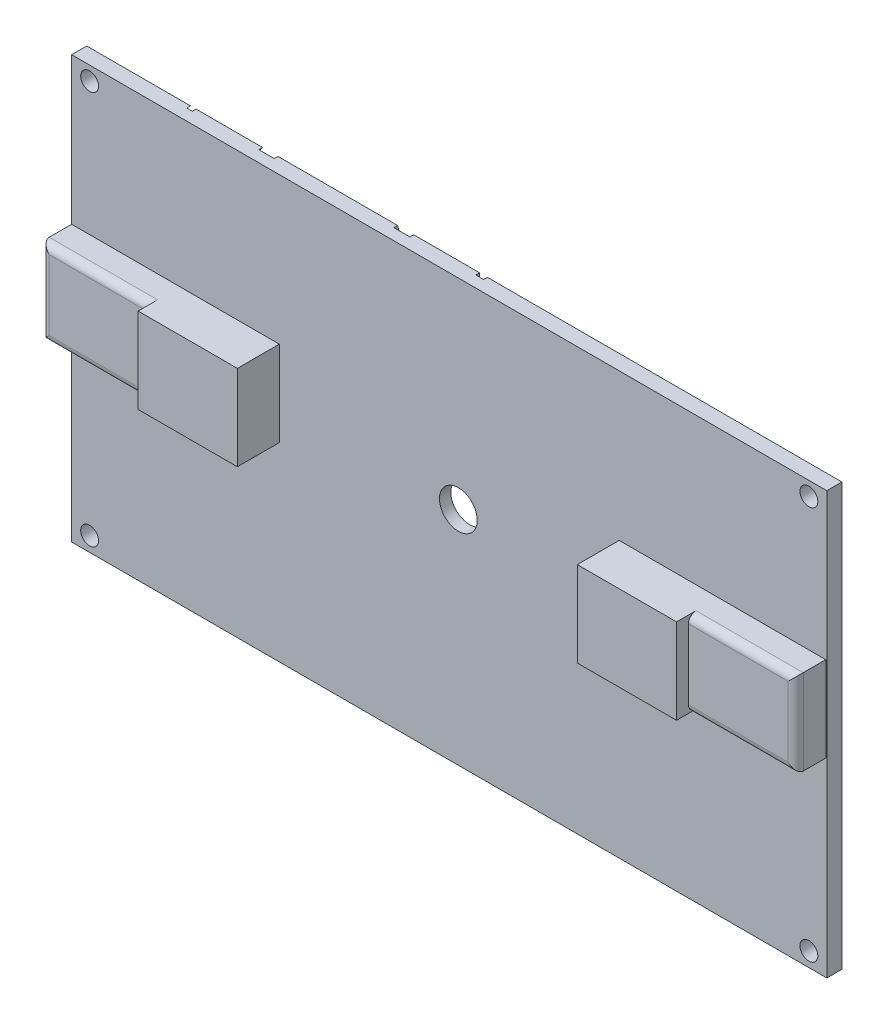
SolidWorks part; units mm, degrees
note: The reader was unsure of these and kept them because the rebuilt part matched: shared geometry of "Sketch2<4>".
ref_plane "Front Plane" through (0, 0, 0) normal (0, 0, 1) x (1, 0, 0)
ref_plane "Top Plane" through (0, 0, 0) normal (0, 1, 0) x (1, 0, 0)
ref_plane "Right Plane" through (0, 0, 0) normal (1, 0, 0) x (0, 0, -1)
sketch "Sketch1" plane through (0, 0, 0) normal (0, 0, 1) x (1, 0, 0)
  line L0 (-63.5, 34.2153) -> (63.5, 34.2153)
  line L1 (-63.5, 34.2153) -> (-63.5, -36.7553)
  line L2 (63.5, 34.2153) -> (63.5, -36.7553)
  line L3 (-63.5, -36.7553) -> (63.5, -36.7553)
  line L5 (63.5, -36.7553) -> (-63.5, -36.7553) construction
  line L18 (-53.34, 34.2153) -> (-63.5, 34.2153) construction
  circle A0 centre (-60.4829, 31.8742) radius 1.5
  circle A1 centre (60.4829, 31.8742) radius 1.5
  circle A2 centre (60.4829, -34.3039) radius 1.5
  circle A3 centre (-60.4829, -34.3039) radius 1.5
extrude "Boss-Extrude1" add sketch "Sketch1" along normal blind 2.54
sketch "Sketch2" plane through (0, 0, 2.54) normal (0, 0, 1) x (1, 0, 0)
  line L4 (-28.5843, 9.5211) -> (-45.2716, 9.5211)
  line L5 (-28.5843, 9.5211) -> (-28.5843, -4.8138)
  line L7 (-45.2716, 9.5211) -> (-45.2716, -4.8138)
  line L15 (-45.2716, 9.5211) -> (-45.2716, -4.8138)
  line L16 (0, 36.7553) -> (0, -36.7553)
  line L17 (-63.5, -36.7553) -> (63.5, -36.7553) construction
  line L22 (-28.5843, -4.8138) -> (-45.2716, -4.8138)
  line L23 (45.2716, 9.5211) -> (45.2716, -4.8138)
  line L24 (28.5843, -4.8138) -> (45.2716, -4.8138)
  line L25 (28.5843, 9.5211) -> (28.5843, -4.8138)
  line L26 (28.5843, 9.5211) -> (45.2716, 9.5211)
  line L27 (-45.2716, 9.5211) -> (-63.5092, 9.5211)
  line L28 (-45.2716, -4.8138) -> (-63.5092, -4.8138)
  line L29 (-63.5092, 9.5211) -> (-63.5092, -4.8138)
  line L30 (45.2716, 9.5211) -> (45.2716, -4.8138)
  line L31 (45.2716, 9.5211) -> (63.3189, 9.5211)
  line L32 (45.2716, -4.8138) -> (63.3189, -4.8138)
  line L33 (63.3189, 9.5211) -> (63.3189, -4.8138)
  point P13 (0, 0)
  point P19 (0, 0)
  line M8 (-63.5, 34.2153) -> (-63.5, -36.7553)
extrude "Boss-Extrude2" add sketch "Sketch2" along normal up to surface (7.05 mm away) contours L22 L5 L4 L7 | L26 L25 L24 L23
sketch "Sketch5" plane through (0, 0, 0) normal (0, 0, -1) x (-1, 0, 0)
  line L0 (-36.885, -13.4809) -> (-37.1458, -14.3716)
  line L1 (-37.1458, -14.3716) -> (-36.8589, -14.6391)
  line L2 (-27.5225, -14.1108) -> (-27.83, -13.4309)
  line L4 (-31.7769, -13.0748) -> (-31.7416, -14.0911)
  line L5 (-32.5586, -12.7895) -> (-32.5586, -11.5305)
  line L6 (-40.1865, -10.7947) -> (-40.5841, -11.2787)
  line L7 (-24.1261, -11.1687) -> (-24.6946, -10.6003)
  line L9 (-28.8243, -9.1813) -> (-28.4608, -9.8868)
  line L10 (-28.4608, -9.8868) -> (-27.9672, -9.3035)
  line L11 (-39.308, -8.9338) -> (-39.0341, -8.7828)
  line L12 (-40.0462, -9.507) -> (-39.308, -8.9338)
  line L14 (-32.7102, -6.0212) -> (-32.7102, -4.7967)
  line L15 (-30.3226, -4.27) -> (-29.7412, -6.9873)
  line L16 (-35.3662, -3.9608) -> (-35.7336, -5.255)
  line L17 (-32.05, -1.5921) -> (-30.4169, -0.7505)
  line L18 (-32.8547, 1.5812) -> (-32.6594, 1.6396)
  line L19 (-31.2175, 1.5222) -> (-30.8977, 2.9206)
  line L21 (-28.2771, 4.5462) -> (-27.9991, 5.1262)
  line L24 (-30.2374, 5.2517) -> (-30.134, 5.4911)
  spline S0 degree 3 poles (-33.1885, -17.143) (-34.1932, -17.0103) (-34.7116, -16.8535) (-35.6221, -16.4098) knots 0 0 0 0 0.058824 0.058824 0.058824 0.058824
  spline S1 degree 3 poles (-35.6221, -16.4098) (-36.8909, -15.7906) (-39.1899, -14.0879) (-40.2119, -13.0118) knots 0.058824 0.058824 0.058824 0.058824 0.117647 0.117647 0.117647 0.117647
  spline S2 degree 3 poles (-40.2119, -13.0118) (-42.0998, -11.0241) (-43.4284, -8.8127) (-44.5933, -6.0588) knots 0.117647 0.117647 0.117647 0.117647 0.176471 0.176471 0.176471 0.176471
  spline S3 degree 3 poles (-44.5933, -6.0588) (-46.4838, -1.5902) (-46.9882, 2.0987) (-46.9916, 7.2423) knots 0.176471 0.176471 0.176471 0.176471 0.235294 0.235294 0.235294 0.235294
  spline S4 degree 3 poles (-46.9916, 7.2423) (-46.9929, 9.1941) (-46.9384, 10.3368) (-46.6702, 11.9282) knots 0.235294 0.235294 0.235294 0.235294 0.294118 0.294118 0.294118 0.294118
  spline S5 degree 3 poles (-46.6702, 11.9282) (-46.2271, 14.5594) (-45.4891, 16.6557) (-44.1889, 18.9752) knots 0.294118 0.294118 0.294118 0.294118 0.352941 0.352941 0.352941 0.352941
  spline S6 degree 3 poles (-44.1889, 18.9752) (-42.1802, 22.5589) (-39.5745, 24.3329) (-35.4062, 25.1243) knots 0.352941 0.352941 0.352941 0.352941 0.411765 0.411765 0.411765 0.411765
  spline S7 degree 3 poles (-35.4062, 25.1243) (-32.345, 25.7055) (-28.2421, 25.2315) (-25.7811, 24.0137) knots 0.411765 0.411765 0.411765 0.411765 0.470588 0.470588 0.470588 0.470588
  spline S8 degree 3 poles (-25.7811, 24.0137) (-23.4916, 22.8808) (-21.2928, 20.156) (-20.2719, 17.5728) knots 0.470588 0.470588 0.470588 0.470588 0.529412 0.529412 0.529412 0.529412
  spline S9 degree 3 poles (-20.2719, 17.5728) (-19.4845, 15.5796) (-18.8834, 13.1051) (-18.6988, 11.0973) knots 0.529412 0.529412 0.529412 0.529412 0.588235 0.588235 0.588235 0.588235
  spline S10 degree 3 poles (-18.6988, 11.0973) (-18.611, 10.1466) (-18.5766, 5.6765) (-18.6463, 4.365) knots 0.588235 0.588235 0.588235 0.588235 0.647059 0.647059 0.647059 0.647059
  spline S11 degree 3 poles (-18.6463, 4.365) (-18.8456, 0.6315) (-19.5099, -2.7362) (-20.7517, -6.3131) knots 0.647059 0.647059 0.647059 0.647059 0.705882 0.705882 0.705882 0.705882
  spline S12 degree 3 poles (-20.7517, -6.3131) (-21.6686, -8.9526) (-22.4464, -10.3502) (-23.9554, -12.0678) knots 0.705882 0.705882 0.705882 0.705882 0.764706 0.764706 0.764706 0.764706
  spline S13 degree 3 poles (-23.9554, -12.0678) (-25.7017, -14.0551) (-26.815, -14.7587) (-28.7545, -16.0654) knots 0.764706 0.764706 0.764706 0.764706 0.823529 0.823529 0.823529 0.823529
  spline S14 degree 3 poles (-28.7545, -16.0654) (-29.6402, -16.6615) (-30.2709, -16.9209) (-31.1354, -17.0447) knots 0.823529 0.823529 0.823529 0.823529 0.882353 0.882353 0.882353 0.882353
  spline S15 degree 3 poles (-31.1354, -17.0447) (-31.64, -17.1176) (-32.9193, -17.1783) (-33.1885, -17.143) knots 0.882353 0.882353 0.882353 0.882353 1 1 1 1
  spline S16 degree 3 poles (-32.4855, -15.8005) (-32.534, -14.6332) (-32.4987, -14.7252) (-32.9825, -14.502) knots 0 0 0 0 0.142857 0.142857 0.142857 0.142857
  spline S17 degree 3 poles (-32.9825, -14.502) (-34.4925, -13.8043) (-35.6396, -13.5475) (-36.885, -13.4809) knots 0.142857 0.142857 0.142857 0.142857 0.285714 0.285714 0.285714 0.285714
  spline S18 degree 3 poles (-36.8589, -14.6391) (-35.827, -15.5987) (-34.0406, -16.3533) (-32.5462, -16.4614) knots 0.571429 0.571429 0.571429 0.571429 0.714286 0.714286 0.714286 0.714286
  spline S19 degree 3 poles (-32.5462, -16.4614) (-32.4649, -16.4673) (-32.4601, -16.4148) (-32.4855, -15.8005) knots 0.714286 0.714286 0.714286 0.714286 1 1 1 1
  spline S20 degree 3 poles (-30.8024, -16.1563) (-30.1643, -15.9317) (-29.4926, -15.5921) (-28.8864, -15.1869) knots 0 0 0 0 0.142857 0.142857 0.142857 0.142857
  spline S21 degree 3 poles (-28.8864, -15.1869) (-28.2116, -14.7359) (-27.5258, -14.1944) (-27.5225, -14.1108) knots 0.142857 0.142857 0.142857 0.142857 0.285714 0.285714 0.285714 0.285714
  spline S22 degree 3 poles (-27.83, -13.4309) (-29.6027, -13.6122) (-30.2155, -13.9611) (-31.8031, -14.7546) knots 0.428571 0.428571 0.428571 0.428571 0.571429 0.571429 0.571429 0.571429
  spline S23 degree 3 poles (-31.8031, -14.7546) (-31.8031, -15.0363) (-31.8511, -16.302) (-31.7761, -16.377) knots 0.571429 0.571429 0.571429 0.571429 0.714286 0.714286 0.714286 0.714286
  spline S24 degree 3 poles (-31.7761, -16.377) (-31.7301, -16.423) (-31.2528, -16.3156) (-30.8024, -16.1563) knots 0.714286 0.714286 0.714286 0.714286 1 1 1 1
  spline S25 degree 3 poles (-29.7616, -13.2038) (-27.6822, -12.7041) (-27.7167, -13.5177) (-28.4018, -11.8782) knots 0 0 0 0 0.142857 0.142857 0.142857 0.142857
  spline S27 degree 3 poles (-31.1978, -11.4148) (-31.8861, -11.7602) (-31.8286, -11.5968) (-31.7769, -13.0748) knots 0.428571 0.428571 0.428571 0.428571 0.571429 0.571429 0.571429 0.571429
  spline S28 degree 3 poles (-31.7416, -14.0911) (-31.1726, -13.8005) (-30.2292, -13.3153) (-29.7616, -13.2038) knots 0.714286 0.714286 0.714286 0.714286 1 1 1 1
  spline S29 degree 3 poles (-32.5586, -11.5305) (-33.91, -10.8515) (-34.3275, -10.9556) (-35.9543, -10.9497) knots 0.142857 0.142857 0.142857 0.142857 0.285714 0.285714 0.285714 0.285714
  spline S30 degree 3 poles (-35.9543, -10.9497) (-36.0729, -11.261) (-36.7649, -12.9501) (-36.7022, -13.0133) knots 0.285714 0.285714 0.285714 0.285714 0.428571 0.428571 0.428571 0.428571
  spline S31 degree 3 poles (-36.7022, -13.0133) (-36.6867, -13.0282) (-36.5069, -13.0412) (-36.3028, -13.0412) knots 0.428571 0.428571 0.428571 0.428571 0.571429 0.571429 0.571429 0.571429
  spline S32 degree 3 poles (-36.3028, -13.0412) (-34.1419, -13.0412) (-33.0415, -13.9931) (-32.5962, -14.0445) knots 0.571429 0.571429 0.571429 0.571429 0.714286 0.714286 0.714286 0.714286
  spline S33 degree 3 poles (-32.5962, -14.0445) (-32.5758, -14.0468) (-32.5586, -13.4826) (-32.5586, -12.7895) knots 0.714286 0.714286 0.714286 0.714286 1 1 1 1
  spline S34 degree 3 poles (-37.6832, -13.7696) (-37.5454, -13.4809) (-37.5716, -13.0643) (-37.7463, -12.759) knots 0 0 0 0 0.142857 0.142857 0.142857 0.142857
  spline S35 degree 3 poles (-37.7463, -12.759) (-38.0466, -12.235) (-39.9648, -10.4193) (-40.1865, -10.7947) knots 0.142857 0.142857 0.142857 0.142857 0.285714 0.285714 0.285714 0.285714
  spline S36 degree 3 poles (-40.5841, -11.2787) (-40.1635, -11.9147) (-39.6844, -12.5177) (-39.1061, -12.9969) knots 0.428571 0.428571 0.428571 0.428571 0.571429 0.571429 0.571429 0.571429
  spline S37 degree 3 poles (-39.1061, -12.9969) (-38.6207, -13.3996) (-37.8677, -13.9485) (-37.7997, -13.9485) knots 0.571429 0.571429 0.571429 0.571429 0.714286 0.714286 0.714286 0.714286
  spline S38 degree 3 poles (-37.7997, -13.9485) (-37.7825, -13.9485) (-37.73, -13.8681) (-37.6832, -13.7696) knots 0.714286 0.714286 0.714286 0.714286 1 1 1 1
  spline S39 degree 3 poles (-26.2446, -13.4366) (-25.5545, -12.9738) (-24.5004, -11.8071) (-24.1261, -11.1687) knots 0 0 0 0 0.166667 0.166667 0.166667 0.166667
  spline S40 degree 3 poles (-24.6946, -10.6003) (-25.3891, -10.9385) (-26.2233, -11.6423) (-26.6867, -12.4121) knots 0.333333 0.333333 0.333333 0.333333 0.5 0.5 0.5 0.5
  spline S41 degree 3 poles (-26.6867, -12.4121) (-27.0847, -13.0732) (-26.6331, -13.6457) (-26.5826, -13.6457) knots 0.5 0.5 0.5 0.5 0.666667 0.666667 0.666667 0.666667
  spline S42 degree 3 poles (-26.5826, -13.6457) (-26.5677, -13.6457) (-26.4161, -13.5515) (-26.2446, -13.4366) knots 0.666667 0.666667 0.666667 0.666667 1 1 1 1
  spline S43 degree 3 poles (-37.1901, -12.2973) (-37.0062, -11.8168) (-36.694, -10.683) (-36.8433, -10.2919) knots 0 0 0 0 0.166667 0.166667 0.166667 0.166667
  spline S44 degree 3 poles (-36.8433, -10.2919) (-36.913, -10.1075) (-37.4698, -9.562) (-37.7619, -9.3913) knots 0.166667 0.166667 0.166667 0.166667 0.333333 0.333333 0.333333 0.333333
  spline S45 degree 3 poles (-37.7619, -9.3913) (-38.43, -9.0016) (-38.869, -9.6263) (-39.532, -10.2518) knots 0.333333 0.333333 0.333333 0.333333 0.5 0.5 0.5 0.5
  spline S46 degree 3 poles (-39.532, -10.2518) (-38.7493, -10.782) (-37.8147, -11.4465) (-37.4568, -12.1217) knots 0.5 0.5 0.5 0.5 0.666667 0.666667 0.666667 0.666667
  spline S47 degree 3 poles (-37.4568, -12.1217) (-37.3159, -12.3876) (-37.2922, -12.5683) (-37.1901, -12.2973) knots 0.666667 0.666667 0.666667 0.666667 1 1 1 1
  spline S49 degree 3 poles (-25.2974, -10.1524) (-25.5981, -9.8388) (-26.2691, -9.2125) (-26.5095, -9.1364) knots 0.166667 0.166667 0.166667 0.166667 0.333333 0.333333 0.333333 0.333333
  spline S50 degree 3 poles (-26.5095, -9.1364) (-26.6786, -9.083) (-27.206, -9.3995) (-27.6037, -9.7917) knots 0.333333 0.333333 0.333333 0.333333 0.5 0.5 0.5 0.5
  spline S52 degree 3 poles (-27.5577, -11.6674) (-27.1975, -12.4128) (-27.3214, -12.4753) (-26.9591, -11.7994) knots 0.666667 0.666667 0.666667 0.666667 1 1 1 1
  spline S53 degree 3 poles (-31.3693, -10.6759) (-30.544, -10.3198) (-29.9421, -10.2965) (-29.0718, -10.2543) knots 0 0 0 0 0.166667 0.166667 0.166667 0.166667
  spline S55 degree 3 poles (-30.1005, -7.9322) (-30.565, -7.5949) (-32.033, -8.1301) (-31.9335, -8.3866) knots 0.333333 0.333333 0.333333 0.333333 0.5 0.5 0.5 0.5
  spline S57 degree 3 poles (-32.7028, -9.5382) (-32.7544, -7.9651) (-32.7841, -7.8112) (-33.8266, -7.7609) knots 0 0 0 0 0.142857 0.142857 0.142857 0.142857
  spline S59 degree 3 poles (-35.3506, -9.0822) (-35.8526, -10.4299) (-35.9628, -10.2508) (-34.9651, -10.2788) knots 0.285714 0.285714 0.285714 0.285714 0.428571 0.428571 0.428571 0.428571
  spline S60 degree 3 poles (-34.9651, -10.2788) (-34.1139, -10.3027) (-34.2699, -10.2745) (-33.4657, -10.556) knots 0.428571 0.428571 0.428571 0.428571 0.571429 0.571429 0.571429 0.571429
  spline S61 degree 3 poles (-33.4657, -10.556) (-33.0638, -10.6971) (-32.7192, -10.7973) (-32.6997, -10.7792) knots 0.571429 0.571429 0.571429 0.571429 0.714286 0.714286 0.714286 0.714286
  spline S63 degree 3 poles (-41.0263, -10.7233) (-40.9755, -10.6963) (-40.8279, -10.5331) (-40.6982, -10.3609) knots 0 0 0 0 0.125 0.125 0.125 0.125
  spline S64 degree 3 poles (-40.6982, -10.3609) (-40.4176, -9.9876) (-40.4193, -9.936) (-40.7317, -9.4152) knots 0.125 0.125 0.125 0.125 0.25 0.25 0.25 0.25
  spline S65 degree 3 poles (-40.7317, -9.4152) (-41.0574, -8.8714) (-41.575, -8.2505) (-41.8383, -8.088) knots 0.25 0.25 0.25 0.25 0.375 0.375 0.375 0.375
  spline S66 degree 3 poles (-41.8383, -8.088) (-42.1056, -7.9232) (-42.9079, -7.6313) (-42.9282, -7.6912) knots 0.375 0.375 0.375 0.375 0.5 0.5 0.5 0.5
  spline S67 degree 3 poles (-42.9282, -7.6912) (-42.9522, -7.7609) (-42.5912, -8.6121) (-42.3262, -9.1101) knots 0.5 0.5 0.5 0.5 0.625 0.625 0.625 0.625
  spline S68 degree 3 poles (-42.3262, -9.1101) (-42.0065, -9.7138) (-41.6932, -10.1886) (-41.3969, -10.5167) knots 0.625 0.625 0.625 0.625 0.75 0.75 0.75 0.75
  spline S69 degree 3 poles (-41.3969, -10.5167) (-41.1421, -10.8004) (-41.1559, -10.793) (-41.0263, -10.7233) knots 0.75 0.75 0.75 0.75 1 1 1 1
  spline S70 degree 3 poles (-23.4839, -10.383) (-22.9736, -9.803) (-21.8591, -7.6985) (-21.9918, -7.5664) knots 0 0 0 0 0.2 0.2 0.2 0.2
  spline S71 degree 3 poles (-21.9918, -7.5664) (-22.0287, -7.5295) (-22.7743, -7.7445) (-22.9843, -7.8518) knots 0.2 0.2 0.2 0.2 0.4 0.4 0.4 0.4
  spline S74 degree 3 poles (-36.1462, -9.5013) (-36.0302, -9.223) (-35.4667, -7.9213) (-35.5883, -7.7033) knots 0 0 0 0 0.2 0.2 0.2 0.2
  spline S75 degree 3 poles (-35.5883, -7.7033) (-35.7448, -7.4227) (-36.3024, -7.2794) (-36.6661, -7.2399) knots 0.2 0.2 0.2 0.2 0.4 0.4 0.4 0.4
  spline S76 degree 3 poles (-36.6661, -7.2399) (-37.8207, -8.7342) (-38.6837, -8.311) (-37.6707, -8.8263) knots 0.4 0.4 0.4 0.4 0.6 0.6 0.6 0.6
  spline S77 degree 3 poles (-37.6707, -8.8263) (-36.2885, -9.5298) (-36.4852, -10.3247) (-36.1462, -9.5013) knots 0.6 0.6 0.6 0.6 1 1 1 1
  spline S79 degree 3 poles (-26.9269, -8.2824) (-27.648, -7.9423) (-28.1494, -6.859) (-28.9922, -7.3934) knots 0.166667 0.166667 0.166667 0.166667 0.333333 0.333333 0.333333 0.333333
  spline S81 degree 3 poles (-39.0341, -8.7828) (-39.544, -8.7577) (-40.2985, -8.6688) (-40.5743, -8.5499) knots 0.2 0.2 0.2 0.2 0.4 0.4 0.4 0.4
  spline S82 degree 3 poles (-40.5743, -8.5499) (-41.2357, -8.2647) (-40.5004, -8.786) (-40.0462, -9.507) knots 0.4 0.4 0.4 0.4 0.6 0.6 0.6 0.6
  spline S84 degree 3 poles (-25.8534, -8.6369) (-25.9151, -8.6984) (-25.2754, -8.8894) (-25.0595, -9.1469) knots 0.4 0.4 0.4 0.4 0.6 0.6 0.6 0.6
  spline S85 degree 3 poles (-25.0595, -9.1469) (-24.8511, -9.3938) (-24.8306, -9.3865) (-24.5665, -8.9722) knots 0.6 0.6 0.6 0.6 1 1 1 1
  spline S86 degree 3 poles (-31.425, -7.2227) (-31.1311, -7.1656) (-30.2915, -7.1967) (-30.2915, -7.1941) knots 0 0 0 0 0.166667 0.166667 0.166667 0.166667
  spline S87 degree 3 poles (-30.2915, -7.1941) (-30.2915, -7.1169) (-30.8444, -4.6678) (-30.8715, -4.6235) knots 0.166667 0.166667 0.166667 0.166667 0.333333 0.333333 0.333333 0.333333
  spline S88 degree 3 poles (-30.8715, -4.6235) (-30.9698, -4.4647) (-31.7349, -4.6441) (-32.0049, -4.736) knots 0.333333 0.333333 0.333333 0.333333 0.5 0.5 0.5 0.5
  spline S89 degree 3 poles (-32.0049, -4.736) (-32.0049, -5.2429) (-32.0736, -7.3732) (-31.9163, -7.3268) knots 0.5 0.5 0.5 0.5 0.666667 0.666667 0.666667 0.666667
  spline S90 degree 3 poles (-31.9163, -7.3268) (-31.868, -7.313) (-31.6465, -7.2661) (-31.425, -7.2227) knots 0.666667 0.666667 0.666667 0.666667 1 1 1 1
  spline S91 degree 3 poles (-32.7102, -4.7967) (-34.1565, -4.3301) (-33.9232, -4.5892) (-34.2932, -5.8703) knots 0.142857 0.142857 0.142857 0.142857 0.285714 0.285714 0.285714 0.285714
  spline S93 degree 3 poles (-34.6033, -7.0144) (-34.636, -7.1941) (-34.6312, -7.208) (-34.5443, -7.1736) knots 0.428571 0.428571 0.428571 0.428571 0.571429 0.571429 0.571429 0.571429
  spline S95 degree 3 poles (-32.7725, -7.2416) (-32.7243, -7.245) (-32.7102, -6.9693) (-32.7102, -6.0212) knots 0.714286 0.714286 0.714286 0.714286 1 1 1 1
  spline S96 degree 3 poles (-29.0941, -6.5273) (-28.6897, -6.4338) (-28.8108, -6.4448) (-29.1014, -5.6471) knots 0 0 0 0 0.2 0.2 0.2 0.2
  spline S97 degree 3 poles (-29.1014, -5.6471) (-29.6437, -4.1585) (-29.3659, -3.5407) (-30.3226, -4.27) knots 0.2 0.2 0.2 0.2 0.4 0.4 0.4 0.4
  spline S98 degree 3 poles (-29.7412, -6.9873) (-29.7409, -6.9888) (-29.4018, -6.5981) (-29.0941, -6.5273) knots 0.6 0.6 0.6 0.6 1 1 1 1
  spline S99 degree 3 poles (-35.0823, -6.592) (-34.8855, -5.944) (-34.614, -4.7538) (-34.6067, -4.5071) knots 0 0 0 0 0.166667 0.166667 0.166667 0.166667
  spline S100 degree 3 poles (-34.6067, -4.5071) (-34.5963, -4.1455) (-34.7391, -4.1723) (-35.3662, -3.9608) knots 0.166667 0.166667 0.166667 0.166667 0.333333 0.333333 0.333333 0.333333
  spline S101 degree 3 poles (-35.7336, -5.255) (-36.4029, -7.0592) (-36.1231, -6.1325) (-35.4398, -6.7683) knots 0.5 0.5 0.5 0.5 0.666667 0.666667 0.666667 0.666667
  spline S102 degree 3 poles (-35.4398, -6.7683) (-35.1622, -7.0266) (-35.2038, -6.9907) (-35.0823, -6.592) knots 0.666667 0.666667 0.666667 0.666667 1 1 1 1
  spline S103 degree 3 poles (-39.1267, -5.5545) (-36.8622, -5.0869) (-35.39, -1.9574) (-36.1158, 0.0639) knots 0 0 0 0 0.125 0.125 0.125 0.125
  spline S104 degree 3 poles (-36.1158, 0.0639) (-36.4504, 0.9964) (-36.9884, 1.8823) (-37.9366, 3.0617) knots 0.125 0.125 0.125 0.125 0.25 0.25 0.25 0.25
  spline S105 degree 3 poles (-37.9366, 3.0617) (-39.6049, 5.1378) (-41.0341, 6.4115) (-43.4622, 7.9026) knots 0.25 0.25 0.25 0.25 0.375 0.375 0.375 0.375
  spline S106 degree 3 poles (-43.4622, 7.9026) (-45.2972, 9.0294) (-45.1867, 9.9658) (-45.4357, 10.2329) knots 0.375 0.375 0.375 0.375 0.5 0.5 0.5 0.5
  spline S107 degree 3 poles (-45.4357, 10.2329) (-45.4823, 10.282) (-45.6325, 9.8595) (-45.8122, 9.1706) knots 0.5 0.5 0.5 0.5 0.625 0.625 0.625 0.625
  spline S108 degree 3 poles (-45.8122, 9.1706) (-46.3428, 7.1307) (-46.4658, 5.2672) (-46.1904, 3.412) knots 0.625 0.625 0.625 0.625 0.75 0.75 0.75 0.75
  spline S109 degree 3 poles (-46.1904, 3.412) (-45.7116, 0.1923) (-43.6372, -6.4835) (-39.1267, -5.5545) knots 0.75 0.75 0.75 0.75 1 1 1 1
  spline S110 degree 3 poles (-24.7002, -5.4052) (-20.3571, -4.3647) (-18.9082, 3.5793) (-19.5616, 7.444) knots 0 0 0 0 0.125 0.125 0.125 0.125
  spline S111 degree 3 poles (-19.5616, 7.444) (-19.7709, 8.6821) (-20.1311, 9.9316) (-20.4771, 10.6142) knots 0.125 0.125 0.125 0.125 0.25 0.25 0.25 0.25
  spline S112 degree 3 poles (-20.4771, 10.6142) (-20.8251, 9.2389) (-21.1954, 8.9597) (-22.7227, 7.9017) knots 0.25 0.25 0.25 0.25 0.375 0.375 0.375 0.375
  spline S113 degree 3 poles (-22.7227, 7.9017) (-25.2154, 6.1751) (-28.0616, 2.6127) (-28.8832, 0.1608) knots 0.375 0.375 0.375 0.375 0.5 0.5 0.5 0.5
  spline S114 degree 3 poles (-28.8832, 0.1608) (-29.4311, -1.4747) (-29.2442, -2.7772) (-28.2763, -4.0618) knots 0.5 0.5 0.5 0.5 0.625 0.625 0.625 0.625
  spline S115 degree 3 poles (-28.2763, -4.0618) (-27.6996, -4.8269) (-27.0491, -5.3109) (-26.3981, -5.4594) knots 0.625 0.625 0.625 0.625 0.75 0.75 0.75 0.75
  spline S116 degree 3 poles (-26.3981, -5.4594) (-26.0174, -5.5463) (-25.18, -5.5192) (-24.7002, -5.4052) knots 0.75 0.75 0.75 0.75 1 1 1 1
  spline S117 degree 3 poles (-32.7062, -2.4148) (-32.7804, -1.9319) (-32.7727, -2.0679) (-33.3008, -1.9974) knots 0 0 0 0 0.2 0.2 0.2 0.2
  spline S118 degree 3 poles (-33.3008, -1.9974) (-33.4549, -2.4841) (-33.8184, -3.6255) (-33.8184, -3.873) knots 0.2 0.2 0.2 0.2 0.4 0.4 0.4 0.4
  spline S119 degree 3 poles (-33.8184, -3.873) (-33.3546, -3.9894) (-33.1169, -4.0249) (-32.6848, -4.1978) knots 0.4 0.4 0.4 0.4 0.6 0.6 0.6 0.6
  spline S120 degree 3 poles (-32.6848, -4.1978) (-32.6753, -3.6991) (-32.6463, -2.7926) (-32.7062, -2.4148) knots 0.6 0.6 0.6 0.6 1 1 1 1
  spline S121 degree 3 poles (-31.7105, -4.0708) (-30.8112, -3.7845) (-30.9289, -4.3462) (-31.2184, -2.8954) knots 0 0 0 0 0.2 0.2 0.2 0.2
  spline S122 degree 3 poles (-31.2184, -2.8954) (-31.3793, -2.0887) (-31.335, -1.8889) (-31.7006, -1.998) knots 0.2 0.2 0.2 0.2 0.4 0.4 0.4 0.4
  spline S123 degree 3 poles (-31.7006, -1.998) (-32.0255, -2.0956) (-32.0548, -2.2014) (-32.0548, -3.262) knots 0.4 0.4 0.4 0.4 0.6 0.6 0.6 0.6
  spline S124 degree 3 poles (-32.0548, -3.262) (-32.0548, -4.3234) (-32.1782, -4.2167) (-31.7105, -4.0708) knots 0.6 0.6 0.6 0.6 1 1 1 1
  spline S126 degree 3 poles (-34.2113, -1.4657) (-34.509, -1.3697) (-34.528, -1.3943) (-34.8624, -2.322) knots 0.2 0.2 0.2 0.2 0.4 0.4 0.4 0.4
  spline S127 degree 3 poles (-34.8624, -2.322) (-35.3837, -3.7655) (-35.2588, -3.0877) (-34.5853, -3.6196) knots 0.4 0.4 0.4 0.4 0.6 0.6 0.6 0.6
  spline S129 degree 3 poles (-29.9766, -3.4392) (-29.7239, -3.3767) (-29.8741, -3.2177) (-30.006, -2.8511) knots 0 0 0 0 0.166667 0.166667 0.166667 0.166667
  spline S130 degree 3 poles (-30.006, -2.8511) (-30.3683, -1.8434) (-30.2737, -1.4102) (-30.5326, -1.4739) knots 0.166667 0.166667 0.166667 0.166667 0.333333 0.333333 0.333333 0.333333
  spline S131 degree 3 poles (-30.5326, -1.4739) (-30.8041, -1.5413) (-30.8961, -1.6389) (-30.8961, -1.8602) knots 0.333333 0.333333 0.333333 0.333333 0.5 0.5 0.5 0.5
  spline S132 degree 3 poles (-30.8961, -1.8602) (-30.8961, -2.0834) (-30.5145, -3.5515) (-30.4293, -3.6574) knots 0.5 0.5 0.5 0.5 0.666667 0.666667 0.666667 0.666667
  spline S133 degree 3 poles (-30.4293, -3.6574) (-30.3617, -3.7404) (-30.0767, -3.4641) (-29.9766, -3.4392) knots 0.666667 0.666667 0.666667 0.666667 1 1 1 1
  spline S134 degree 3 poles (-30.4169, -0.7505) (-30.1176, 0.7533) (-30.1764, -0.0351) (-30.8624, 0.5683) knots 0.111111 0.111111 0.111111 0.111111 0.222222 0.222222 0.222222 0.222222
  spline S135 degree 3 poles (-30.8624, 0.5683) (-31.0674, 0.7489) (-31.1552, 0.7848) (-31.6604, 0.8988) knots 0.222222 0.222222 0.222222 0.222222 0.333333 0.333333 0.333333 0.333333
  spline S139 degree 3 poles (-33.8184, -1.0246) (-33.4389, -1.42) (-33.0604, -1.3263) (-32.6487, -1.6043) knots 0.666667 0.666667 0.666667 0.666667 0.777778 0.777778 0.777778 0.777778
  spline S140 degree 3 poles (-32.6487, -1.6043) (-32.3615, -1.7982) (-32.3358, -1.7992) (-32.05, -1.5921) knots 0.777778 0.777778 0.777778 0.777778 1 1 1 1
  spline S141 degree 3 poles (-34.2006, 0.9972) (-34.0586, 1.1384) (-34.1136, 1.4426) (-34.5048, 2.6911) knots 0 0 0 0 0.166667 0.166667 0.166667 0.166667
  spline S142 degree 3 poles (-34.5048, 2.6911) (-35.1391, 4.7129) (-34.6933, 3.7976) (-35.6958, 3.4184) knots 0.166667 0.166667 0.166667 0.166667 0.333333 0.333333 0.333333 0.333333
  spline S143 degree 3 poles (-35.6958, 3.4184) (-36.0946, 3.2676) (-35.9123, 3.1341) (-35.6597, 2.6886) knots 0.333333 0.333333 0.333333 0.333333 0.5 0.5 0.5 0.5
  spline S144 degree 3 poles (-35.6597, 2.6886) (-34.7367, 1.0615) (-35.137, 0.9177) (-34.5795, 0.9177) knots 0.5 0.5 0.5 0.5 0.666667 0.666667 0.666667 0.666667
  spline S145 degree 3 poles (-34.5795, 0.9177) (-34.3736, 0.9177) (-34.2548, 0.9431) (-34.2006, 0.9972) knots 0.666667 0.666667 0.666667 0.666667 1 1 1 1
  spline S146 degree 3 poles (-29.8798, 1.1827) (-29.719, 1.4739) (-28.6281, 3.7491) (-28.6281, 3.7918) knots 0 0 0 0 0.166667 0.166667 0.166667 0.166667
  spline S147 degree 3 poles (-28.6281, 3.7918) (-28.6281, 3.8532) (-29.0899, 3.818) (-29.5098, 4.2018) knots 0.166667 0.166667 0.166667 0.166667 0.333333 0.333333 0.333333 0.333333
  spline S148 degree 3 poles (-29.5098, 4.2018) (-29.9217, 4.5785) (-29.7856, 4.6422) (-30.1981, 2.9821) knots 0.333333 0.333333 0.333333 0.333333 0.5 0.5 0.5 0.5
  spline S149 degree 3 poles (-30.1981, 2.9821) (-30.5842, 1.4288) (-30.5966, 1.2803) (-30.3522, 1.1474) knots 0.5 0.5 0.5 0.5 0.666667 0.666667 0.666667 0.666667
  spline S150 degree 3 poles (-30.3522, 1.1474) (-30.1456, 1.035) (-29.9529, 1.0497) (-29.8798, 1.1827) knots 0.666667 0.666667 0.666667 0.666667 1 1 1 1
  spline S152 degree 3 poles (-32.7669, 4.899) (-32.8268, 4.899) (-33.4484, 4.2945) (-33.9282, 4.2945) knots 0.285714 0.285714 0.285714 0.285714 0.428571 0.428571 0.428571 0.428571
  spline S153 degree 3 poles (-33.9282, 4.2945) (-33.9791, 4.2945) (-34.0202, 4.2716) (-34.0202, 4.2428) knots 0.428571 0.428571 0.428571 0.428571 0.571429 0.571429 0.571429 0.571429
  spline S157 degree 3 poles (-31.5079, 4.7776) (-31.6547, 4.8718) (-31.7924, 4.9489) (-31.8139, 4.9489) knots 0.166667 0.166667 0.166667 0.166667 0.333333 0.333333 0.333333 0.333333
  spline S158 degree 3 poles (-31.8139, 4.9489) (-31.8474, 4.9489) (-31.8835, 3.248) (-31.8762, 2.044) knots 0.333333 0.333333 0.333333 0.333333 0.5 0.5 0.5 0.5
  spline S159 degree 3 poles (-31.8762, 2.044) (-31.8725, 1.4229) (-31.6516, 1.5222) (-31.2175, 1.5222) knots 0.5 0.5 0.5 0.5 0.666667 0.666667 0.666667 0.666667
  spline S160 degree 3 poles (-35.6433, 4.1271) (-34.907, 4.587) (-35.2459, 4.9573) (-35.827, 6.1063) knots 0 0 0 0 0.2 0.2 0.2 0.2
  spline S162 degree 3 poles (-36.4315, 3.9279) (-36.1587, 3.9566) (-35.879, 3.9811) (-35.6433, 4.1271) knots 0.6 0.6 0.6 0.6 1 1 1 1
  spline S163 degree 3 poles (-27.9991, 5.1262) (-27.609, 5.9416) (-27.845, 5.5444) (-27.3675, 6.3434) knots 0 0 0 0 0.166667 0.166667 0.166667 0.166667
  spline S164 degree 3 poles (-27.3675, 6.3434) (-27.0093, 6.9425) (-26.8973, 6.9597) (-27.2715, 7.1604) knots 0.166667 0.166667 0.166667 0.166667 0.333333 0.333333 0.333333 0.333333
  spline S167 degree 3 poles (-33.7643, 5.0729) (-33.5084, 5.139) (-33.0866, 5.4119) (-32.8194, 5.5788) knots 0 0 0 0 0.142857 0.142857 0.142857 0.142857
  spline S170 degree 3 poles (-34.5443, 5.2492) (-34.3125, 4.853) (-34.2195, 4.9583) (-33.7643, 5.0729) knots 0.714286 0.714286 0.714286 0.714286 1 1 1 1
extrude "Cut-Extrude1" cut sketch "Sketch5" against normal blind 0.635
sketch "Sketch7" plane through (0, 0, 0) normal (0, 0, -1) x (-1, 0, 0)
  line L0 (-48.7045, 33.1044) -> (-48.7045, -33.6615)
  line L1 (-33.7488, -48.6172) -> (33.3567, -48.6172)
  line L2 (48.3125, -33.6615) -> (48.3125, 33.1044)
  line L3 (33.3567, 48.0601) -> (-33.7488, 48.0601)
  line L4 (19.1455, 5.8466) -> (27.9776, 5.535)
  line L5 (34.9499, -20.3776) -> (24.2152, -35.5754)
  line L6 (22.349, -34.3309) -> (33.6683, -12.3768)
  line L7 (31.1493, -7.2142) -> (24.6188, -6.2198)
  line L8 (-32.027, -16.991) -> (-24.4193, -33.2625)
  line L9 (-28.6808, 5.7223) -> (-20.0986, 5.9086)
  line L10 (13.7349, 22.8248) -> (10.1278, 33.7714)
  spline S0 degree 3 poles (-33.7488, 48.0601) (-42.0345, 48.0601) (-48.7045, 41.3902) (-48.7045, 33.1044) knots 0 0 0 0 1 1 1 1
  spline S1 degree 3 poles (-48.7045, -33.6615) (-48.7045, -41.9471) (-42.0345, -48.6172) (-33.7488, -48.6172) knots 0 0 0 0 1 1 1 1
  spline S2 degree 3 poles (33.3567, -48.6172) (41.6422, -48.6172) (48.3125, -41.9471) (48.3125, -33.6615) knots 0 0 0 0 1 1 1 1
  spline S3 degree 3 poles (48.3125, 33.1044) (48.3125, 41.3902) (41.6422, 48.0601) (33.3567, 48.0601) knots 0 0 0 0 1 1 1 1
  spline S4 degree 3 poles (11.9314, 35.0149) (18.6333, 26.152) (23.5941, 13.0893) (19.1455, 5.8466) knots 0.5 0.5 0.5 0.5 1 1 1 1
  spline S5 degree 3 poles (10.0057, 36.7203) (10.4586, 36.7312) (11.182, 36.1603) (11.9314, 35.0149) knots 0 0 0 0 0.5 0.5 0.5 0.5
  spline S6 degree 3 poles (39.0511, -5.437) (39.5769, -8.5674) (39.0591, -13.1128) (34.9499, -20.3776) knots 0.833333 0.833333 0.833333 0.833333 1 1 1 1
  spline S7 degree 3 poles (21.8827, 0.4353) (29.5291, -1.2382) (38.4594, -1.9155) (39.0511, -5.437) knots 0.666667 0.666667 0.666667 0.666667 0.833333 0.833333 0.833333 0.833333
  spline S8 degree 3 poles (33.2798, 2.9297) (31.7276, 0.5257) (28.4044, 0.6921) (21.8827, 0.4353) knots 0.5 0.5 0.5 0.5 0.666667 0.666667 0.666667 0.666667
  spline S9 degree 3 poles (26.4224, 32.5897) (32.2138, 25.9838) (36.9653, 8.6368) (33.2798, 2.9297) knots 0.333333 0.333333 0.333333 0.333333 0.5 0.5 0.5 0.5
  spline S10 degree 3 poles (24.3088, 30.9106) (23.1793, 33.6794) (23.1063, 36.3055) (26.4224, 32.5897) knots 0.166667 0.166667 0.166667 0.166667 0.333333 0.333333 0.333333 0.333333
  spline S11 degree 3 poles (27.9776, 5.535) (32.7356, 10.4633) (26.9546, 23.8005) (24.3088, 30.9106) knots 0 0 0 0 0.166667 0.166667 0.166667 0.166667
  spline S12 degree 3 poles (24.2152, -35.5754) (22.0587, -37.8135) (21.4791, -36.3746) (22.349, -34.3309) knots 0 0 0 0 1 1 1 1
  spline S13 degree 3 poles (33.6683, -12.3768) (35.3465, -9.313) (34.747, -7.4643) (31.1493, -7.2142) knots 0 0 0 0 1 1 1 1
  spline S14 degree 3 poles (-35.7616, -8.388) (-36.0162, -9.0988) (-34.7538, -12.2673) (-32.027, -16.991) knots 0.916667 0.916667 0.916667 0.916667 1 1 1 1
  spline S15 degree 3 poles (-25.6511, -5.9088) (-31.0497, -5.9319) (-35.194, -6.8067) (-35.7616, -8.388) knots 0.833333 0.833333 0.833333 0.833333 0.916667 0.916667 0.916667 0.916667
  spline S16 degree 3 poles (-15.8436, -32.4275) (-19.7209, -26.2181) (-27.2095, -17.3361) (-25.6511, -5.9088) knots 0.75 0.75 0.75 0.75 0.833333 0.833333 0.833333 0.833333
  spline S17 degree 3 poles (-14.0408, -31.2846) (-12.4871, -34.8012) (-14.5729, -34.6696) (-15.8436, -32.4275) knots 0.666667 0.666667 0.666667 0.666667 0.75 0.75 0.75 0.75
  spline S18 degree 3 poles (-19.8186, -13.0612) (-19.0817, -20.2054) (-16.3431, -25.5487) (-14.0408, -31.2846) knots 0.583333 0.583333 0.583333 0.583333 0.666667 0.666667 0.666667 0.666667
  spline S19 degree 3 poles (-13.9409, -4.1672) (-19.3397, -3.3567) (-21.2191, -6.4084) (-19.8186, -13.0612) knots 0.5 0.5 0.5 0.5 0.583333 0.583333 0.583333 0.583333
  spline S20 degree 3 poles (-1.3715, -30.2282) (-8.657, -29.6054) (-15.5753, -17.9031) (-13.9409, -4.1672) knots 0.416667 0.416667 0.416667 0.416667 0.5 0.5 0.5 0.5
  spline S21 degree 3 poles (12.7856, -4.3693) (15.0651, -21.3611) (4.6078, -30.7387) (-1.3715, -30.2282) knots 0.333333 0.333333 0.333333 0.333333 0.416667 0.416667 0.416667 0.416667
  spline S22 degree 3 poles (18.8546, -7.2721) (18.4144, -4.0523) (14.8026, -4.651) (12.7856, -4.3693) knots 0.25 0.25 0.25 0.25 0.333333 0.333333 0.333333 0.333333
  spline S23 degree 3 poles (12.3977, -31.0347) (16.4864, -23.3035) (19.772, -15.469) (18.8546, -7.2721) knots 0.166667 0.166667 0.166667 0.166667 0.25 0.25 0.25 0.25
  spline S24 degree 3 poles (14.2949, -32.5274) (11.6918, -36.3176) (10.971, -33.7185) (12.3977, -31.0347) knots 0.083333 0.083333 0.083333 0.083333 0.166667 0.166667 0.166667 0.166667
  spline S25 degree 3 poles (24.6188, -6.2198) (25.6872, -15.4848) (20.9778, -24.0846) (14.2949, -32.5274) knots 0 0 0 0 0.083333 0.083333 0.083333 0.083333
  spline S26 degree 3 poles (-30.298, 10.7591) (-30.2629, 7.1465) (-29.3795, 6.7889) (-28.6808, 5.7223) knots 0.888889 0.888889 0.888889 0.888889 1 1 1 1
  spline S27 degree 3 poles (-24.203, 32.7134) (-26.6186, 25.3707) (-30.0965, 18.9537) (-30.298, 10.7591) knots 0.777778 0.777778 0.777778 0.777778 0.888889 0.888889 0.888889 0.888889
  spline S28 degree 3 poles (-25.8202, 33.6777) (-24.528, 35.2259) (-23.3963, 34.8532) (-24.203, 32.7134) knots 0.666667 0.666667 0.666667 0.666667 0.777778 0.777778 0.777778 0.777778
  spline S29 degree 3 poles (-34.534, 15.7718) (-33.2564, 21.3338) (-31.7025, 26.9649) (-25.8202, 33.6777) knots 0.555556 0.555556 0.555556 0.555556 0.666667 0.666667 0.666667 0.666667
  spline S30 degree 3 poles (-34.1677, 3.3302) (-36.1393, 5.7475) (-35.1478, 8.9899) (-34.534, 15.7718) knots 0.444444 0.444444 0.444444 0.444444 0.555556 0.555556 0.555556 0.555556
  spline S31 degree 3 poles (-22.7483, 0.908) (-27.7767, 0.8239) (-32.1468, 0.8524) (-34.1677, 3.3302) knots 0.333333 0.333333 0.333333 0.333333 0.444444 0.444444 0.444444 0.444444
  spline S32 degree 3 poles (-40.1635, -4.2815) (-38.9739, -1.6157) (-29.0298, -0.725) (-22.7483, 0.908) knots 0.222222 0.222222 0.222222 0.222222 0.333333 0.333333 0.333333 0.333333
  spline S33 degree 3 poles (-26.1348, -34.5823) (-31.8952, -26.6685) (-41.5697, -14.5007) (-40.1635, -4.2815) knots 0.111111 0.111111 0.111111 0.111111 0.222222 0.222222 0.222222 0.222222
  spline S34 degree 3 poles (-24.4193, -33.2625) (-22.2963, -37.758) (-25.3633, -35.8934) (-26.1348, -34.5823) knots 0 0 0 0 0.111111 0.111111 0.111111 0.111111
  spline S35 degree 3 poles (6.2098, 6.9659) (20.11, 6.0386) (17.5823, 14.0721) (13.7349, 22.8248) knots 0.857143 0.857143 0.857143 0.857143 1 1 1 1
  spline S36 degree 3 poles (-0.4905, 22.4345) (4.2762, 22.2682) (13.1377, 16.6742) (6.2098, 6.9659) knots 0.714286 0.714286 0.714286 0.714286 0.857143 0.857143 0.857143 0.857143
  spline S37 degree 3 poles (-7.0993, 7.1522) (-13.3651, 15.9882) (-5.1474, 22.5972) (-0.4905, 22.4345) knots 0.571429 0.571429 0.571429 0.571429 0.714286 0.714286 0.714286 0.714286
  spline S38 degree 3 poles (-17.3193, 11.2638) (-16.7452, 8.4909) (-14.0082, 6.7889) (-7.0993, 7.1522) knots 0.428571 0.428571 0.428571 0.428571 0.571429 0.571429 0.571429 0.571429
  spline S39 degree 3 poles (-10.8936, 32.0917) (-12.0413, 27.5732) (-18.4235, 16.599) (-17.3193, 11.2638) knots 0.285714 0.285714 0.285714 0.285714 0.428571 0.428571 0.428571 0.428571
  spline S40 degree 3 poles (-13.3189, 33.5224) (-12.2744, 35.5138) (-7.8378, 40.0996) (-10.8936, 32.0917) knots 0.142857 0.142857 0.142857 0.142857 0.285714 0.285714 0.285714 0.285714
  spline S41 degree 3 poles (-20.0986, 5.9086) (-24.2068, 13.5525) (-18.7866, 25.7992) (-13.3189, 33.5224) knots 0 0 0 0 0.142857 0.142857 0.142857 0.142857
  spline S42 degree 3 poles (10.1278, 33.7714) (9.2903, 35.7289) (9.4244, 36.7051) (10.0057, 36.7203) knots 0 0 0 0 1 1 1 1
sketch "Sketch8" plane through (0, 0, 0) normal (0, 0, -1) x (-1, 0, 0)
  line L22 (1.303, 5.9086) -> (-7.2792, 5.7223)
  line L23 (-3.0177, -33.2625) -> (-10.6254, -16.991)
  line L24 (46.0204, -6.2198) -> (52.5509, -7.2142)
  line L25 (55.0699, -12.3768) -> (43.7506, -34.3309)
  line L26 (45.6168, -35.5754) -> (56.3515, -20.3776)
  line L27 (49.3792, 5.535) -> (40.5471, 5.8466)
  line L28 (31.5294, 33.7714) -> (35.1365, 22.8248)
  spline S86 degree 3 poles (-7.2792, 5.7223) (-7.9779, 6.7889) (-8.8613, 7.1465) (-8.8964, 10.7591) knots 0.888889 0.888889 0.888889 0.888889 1 1 1 1
  spline S87 degree 3 poles (-8.8964, 10.7591) (-8.6949, 18.9537) (-5.217, 25.3707) (-2.8014, 32.7134) knots 0.777778 0.777778 0.777778 0.777778 0.888889 0.888889 0.888889 0.888889
  spline S88 degree 3 poles (-2.8014, 32.7134) (-1.9947, 34.8532) (-3.1264, 35.2259) (-4.4186, 33.6777) knots 0.666667 0.666667 0.666667 0.666667 0.777778 0.777778 0.777778 0.777778
  spline S89 degree 3 poles (-4.4186, 33.6777) (-10.3009, 26.9649) (-11.8548, 21.3338) (-13.1324, 15.7718) knots 0.555556 0.555556 0.555556 0.555556 0.666667 0.666667 0.666667 0.666667
  spline S90 degree 3 poles (-13.1324, 15.7718) (-13.7462, 8.9899) (-14.7377, 5.7475) (-12.7661, 3.3302) knots 0.444444 0.444444 0.444444 0.444444 0.555556 0.555556 0.555556 0.555556
  spline S91 degree 3 poles (-12.7661, 3.3302) (-10.7452, 0.8524) (-6.3751, 0.8239) (-1.3467, 0.908) knots 0.333333 0.333333 0.333333 0.333333 0.444444 0.444444 0.444444 0.444444
  spline S92 degree 3 poles (-1.3467, 0.908) (-7.6282, -0.725) (-17.5723, -1.6157) (-18.7619, -4.2815) knots 0.222222 0.222222 0.222222 0.222222 0.333333 0.333333 0.333333 0.333333
  spline S93 degree 3 poles (-18.7619, -4.2815) (-20.1681, -14.5007) (-10.4936, -26.6685) (-4.7332, -34.5823) knots 0.111111 0.111111 0.111111 0.111111 0.222222 0.222222 0.222222 0.222222
  spline S94 degree 3 poles (-4.7332, -34.5823) (-3.9617, -35.8934) (-0.8947, -37.758) (-3.0177, -33.2625) knots 0 0 0 0 0.111111 0.111111 0.111111 0.111111
  spline S95 degree 3 poles (-10.6254, -16.991) (-13.3522, -12.2673) (-14.6146, -9.0988) (-14.36, -8.388) knots 0.916667 0.916667 0.916667 0.916667 1 1 1 1
  spline S96 degree 3 poles (-14.36, -8.388) (-13.7924, -6.8067) (-9.6481, -5.9319) (-4.2495, -5.9088) knots 0.833333 0.833333 0.833333 0.833333 0.916667 0.916667 0.916667 0.916667
  spline S97 degree 3 poles (-4.2495, -5.9088) (-5.8079, -17.3361) (1.6807, -26.2181) (5.558, -32.4275) knots 0.75 0.75 0.75 0.75 0.833333 0.833333 0.833333 0.833333
  spline S98 degree 3 poles (5.558, -32.4275) (6.8287, -34.6696) (8.9145, -34.8012) (7.3608, -31.2846) knots 0.666667 0.666667 0.666667 0.666667 0.75 0.75 0.75 0.75
  spline S99 degree 3 poles (7.3608, -31.2846) (5.0585, -25.5487) (2.3199, -20.2054) (1.583, -13.0612) knots 0.583333 0.583333 0.583333 0.583333 0.666667 0.666667 0.666667 0.666667
  spline S100 degree 3 poles (1.583, -13.0612) (0.1825, -6.4084) (2.0619, -3.3567) (7.4607, -4.1672) knots 0.5 0.5 0.5 0.5 0.583333 0.583333 0.583333 0.583333
  spline S101 degree 3 poles (7.4607, -4.1672) (5.8263, -17.9031) (12.7446, -29.6054) (20.0301, -30.2282) knots 0.416667 0.416667 0.416667 0.416667 0.5 0.5 0.5 0.5
  spline S102 degree 3 poles (20.0301, -30.2282) (26.0094, -30.7387) (36.4667, -21.3611) (34.1872, -4.3693) knots 0.333333 0.333333 0.333333 0.333333 0.416667 0.416667 0.416667 0.416667
  spline S103 degree 3 poles (34.1872, -4.3693) (36.2042, -4.651) (39.816, -4.0523) (40.2562, -7.2721) knots 0.25 0.25 0.25 0.25 0.333333 0.333333 0.333333 0.333333
  spline S104 degree 3 poles (40.2562, -7.2721) (41.1736, -15.469) (37.888, -23.3035) (33.7993, -31.0347) knots 0.166667 0.166667 0.166667 0.166667 0.25 0.25 0.25 0.25
  spline S105 degree 3 poles (33.7993, -31.0347) (32.3726, -33.7185) (33.0934, -36.3176) (35.6965, -32.5274) knots 0.083333 0.083333 0.083333 0.083333 0.166667 0.166667 0.166667 0.166667
  spline S106 degree 3 poles (35.6965, -32.5274) (42.3794, -24.0846) (47.0888, -15.4848) (46.0204, -6.2198) knots 0 0 0 0 0.083333 0.083333 0.083333 0.083333
  spline S107 degree 3 poles (52.5509, -7.2142) (56.1486, -7.4643) (56.7481, -9.313) (55.0699, -12.3768) knots 0 0 0 0 1 1 1 1
  spline S108 degree 3 poles (43.7506, -34.3309) (42.8807, -36.3746) (43.4603, -37.8135) (45.6168, -35.5754) knots 0 0 0 0 1 1 1 1
  spline S109 degree 3 poles (56.3515, -20.3776) (60.4607, -13.1128) (60.9785, -8.5674) (60.4527, -5.437) knots 0.833333 0.833333 0.833333 0.833333 1 1 1 1
  spline S110 degree 3 poles (60.4527, -5.437) (59.861, -1.9155) (50.9307, -1.2382) (43.2843, 0.4353) knots 0.666667 0.666667 0.666667 0.666667 0.833333 0.833333 0.833333 0.833333
  spline S111 degree 3 poles (43.2843, 0.4353) (49.806, 0.6921) (53.1292, 0.5257) (54.6814, 2.9297) knots 0.5 0.5 0.5 0.5 0.666667 0.666667 0.666667 0.666667
  spline S112 degree 3 poles (54.6814, 2.9297) (58.3669, 8.6368) (53.6154, 25.9838) (47.824, 32.5897) knots 0.333333 0.333333 0.333333 0.333333 0.5 0.5 0.5 0.5
  spline S113 degree 3 poles (47.824, 32.5897) (44.5079, 36.3055) (44.5809, 33.6794) (45.7104, 30.9106) knots 0.166667 0.166667 0.166667 0.166667 0.333333 0.333333 0.333333 0.333333
  spline S114 degree 3 poles (45.7104, 30.9106) (48.3562, 23.8005) (54.1372, 10.4633) (49.3792, 5.535) knots 0 0 0 0 0.166667 0.166667 0.166667 0.166667
  spline S115 degree 3 poles (40.5471, 5.8466) (44.9957, 13.0893) (40.0349, 26.152) (33.333, 35.0149) knots 0.5 0.5 0.5 0.5 1 1 1 1
  spline S116 degree 3 poles (33.333, 35.0149) (32.5836, 36.1603) (31.8602, 36.7312) (31.4073, 36.7203) knots 0 0 0 0 0.5 0.5 0.5 0.5
  spline S117 degree 3 poles (31.4073, 36.7203) (30.826, 36.7051) (30.6919, 35.7289) (31.5294, 33.7714) knots 0 0 0 0 1 1 1 1
  spline S118 degree 3 poles (35.1365, 22.8248) (38.9839, 14.0721) (41.5116, 6.0386) (27.6114, 6.9659) knots 0.857143 0.857143 0.857143 0.857143 1 1 1 1
  spline S119 degree 3 poles (27.6114, 6.9659) (34.5393, 16.6742) (25.6778, 22.2682) (20.9111, 22.4345) knots 0.714286 0.714286 0.714286 0.714286 0.857143 0.857143 0.857143 0.857143
  spline S120 degree 3 poles (20.9111, 22.4345) (16.2542, 22.5972) (8.0365, 15.9882) (14.3023, 7.1522) knots 0.571429 0.571429 0.571429 0.571429 0.714286 0.714286 0.714286 0.714286
  spline S121 degree 3 poles (14.3023, 7.1522) (7.3934, 6.7889) (4.6564, 8.4909) (4.0823, 11.2638) knots 0.428571 0.428571 0.428571 0.428571 0.571429 0.571429 0.571429 0.571429
  spline S122 degree 3 poles (4.0823, 11.2638) (2.9781, 16.599) (9.3603, 27.5732) (10.508, 32.0917) knots 0.285714 0.285714 0.285714 0.285714 0.428571 0.428571 0.428571 0.428571
  spline S123 degree 3 poles (10.508, 32.0917) (13.5638, 40.0996) (9.1272, 35.5138) (8.0827, 33.5224) knots 0.142857 0.142857 0.142857 0.142857 0.285714 0.285714 0.285714 0.285714
  spline S124 degree 3 poles (8.0827, 33.5224) (2.615, 25.7992) (-2.8052, 13.5525) (1.303, 5.9086) knots 0 0 0 0 0.142857 0.142857 0.142857 0.142857
extrude "Cut-Extrude3" cut sketch "Sketch8" against normal blind 0.635
sketch "Sketch9" plane through (0, 0, 2.54) normal (0, 0, 1) x (1, 0, 0)
  circle A0 centre (1.5317, 0.4966) radius 3.175
extrude "Cut-Extrude4" cut sketch "Sketch9" against normal blind 5.08
extrude "Boss-Extrude3" add sketch "Sketch2<4>" along normal up to vertex (5.05 mm away) contours L28 L7 L27 M8 | L33 L31 L23 L32
sketch "Sketch2<4>" plane through (0, 0, 2.54) normal (0, 0, 1) x (1, 0, 0) same geometry as "Sketch2"
fillet "Fillet1" radius 1.27 6 edges at (54.2952, 9.5211, 7.59) (63.3189, 2.3537, 7.59) (54.2952, -4.8138, 7.59) (-54.3858, -4.8138, 7.59) (-63.5, 2.3537, 7.59) (-54.3858, 9.5211, 7.59)
